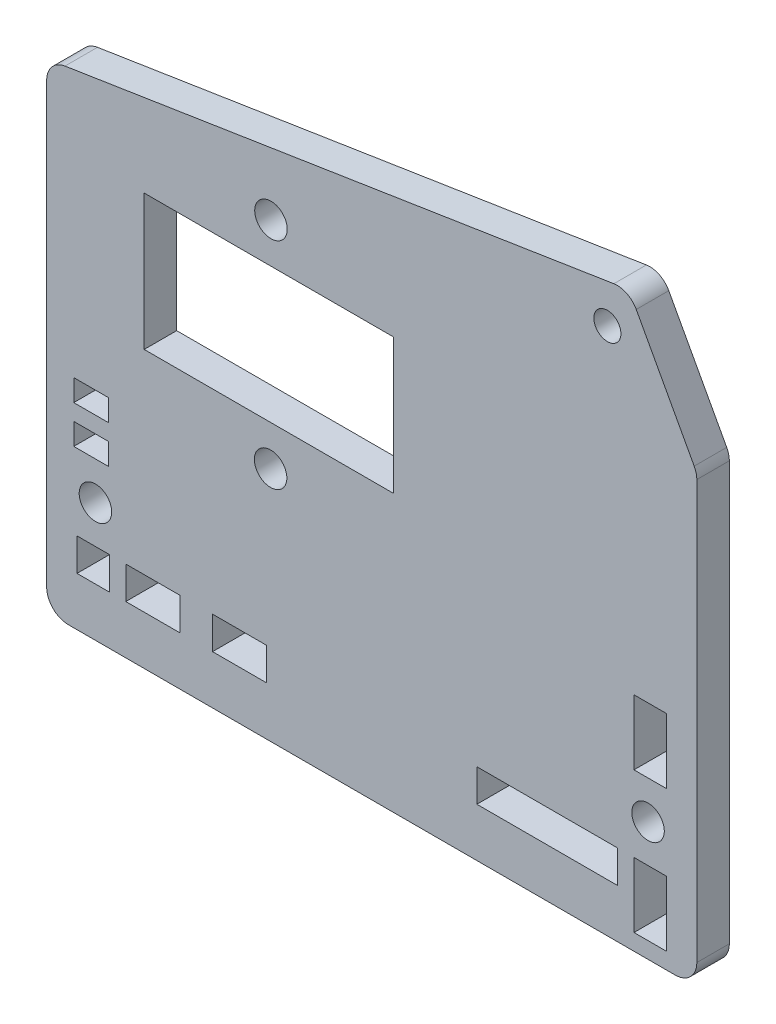
SolidWorks part; units mm, degrees
ref_plane "Plan de face" through (0, 0, 0) normal (0, 0, 1) x (1, 0, 0)
ref_plane "Plan de dessus" through (0, 0, 0) normal (0, 1, 0) x (1, 0, 0)
ref_plane "Plan de droite" through (0, 0, 0) normal (1, 0, 0) x (0, 0, -1)
sketch "Esquisse1" plane through (0, 0, 0) normal (0, 0, 1) x (1, 0, 0)
  line L0 (20.7, 21.5) -> (20.7, 41.7) construction
  line L1 (0, 0) -> (60, 0) construction
  line L2 (0, 0) -> (0, 44.2274) construction
  line L3 (0, 52.5) -> (60, 52.5) construction
  line L4 (60, 0) -> (60, 41.1061) construction
  line L5 (9, 38) -> (32, 38)
  line L6 (9, 38) -> (9, 25.5)
  line L7 (9, 25.5) -> (32, 25.5)
  line L8 (32, 38) -> (32, 25.5)
  line L9 (39.7, 7.5) -> (52.7, 7.5)
  line L10 (39.7, 7.5) -> (39.7, 4.5)
  line L11 (39.7, 4.5) -> (52.7, 4.5)
  line L12 (52.7, 7.5) -> (52.7, 4.5)
  line L13 (54.2, 7.5) -> (57.2, 7.5)
  line L14 (54.2, 7.5) -> (54.2, 1.5)
  line L15 (54.2, 1.5) -> (57.2, 1.5)
  line L16 (57.2, 7.5) -> (57.2, 1.5)
  line L17 (54.2, 20.5) -> (57.2, 20.5)
  line L18 (54.2, 20.5) -> (54.2, 14.5)
  line L19 (54.2, 14.5) -> (57.2, 14.5)
  line L20 (57.2, 20.5) -> (57.2, 14.5)
  line L21 (15.3085, 7.5) -> (20.3085, 7.5)
  line L22 (15.3085, 7.5) -> (15.3085, 4.5)
  line L23 (15.3085, 4.5) -> (20.3085, 4.5)
  line L24 (20.3085, 7.5) -> (20.3085, 4.5)
  line L25 (7.3, 7.5) -> (12.3085, 7.5)
  line L26 (7.3, 7.5) -> (7.3, 4.5)
  line L27 (7.3, 4.5) -> (12.3085, 4.5)
  line L28 (12.3085, 7.5) -> (12.3085, 4.5)
  line L29 (2.8, 7.5) -> (5.8, 7.5)
  line L30 (2.8, 7.5) -> (2.8, 4.5)
  line L31 (2.8, 4.5) -> (5.8, 4.5)
  line L32 (5.8, 7.5) -> (5.8, 4.5)
  line L33 (2.5, 16.5) -> (5.7, 16.5)
  line L34 (2.5, 16.5) -> (2.5, 14.5)
  line L35 (2.5, 14.5) -> (5.7, 14.5)
  line L36 (5.7, 16.5) -> (5.7, 14.5)
  line L37 (2.5, 20) -> (5.7, 20)
  line L38 (2.5, 20) -> (2.5, 18)
  line L39 (2.5, 18) -> (5.7, 18)
  line L40 (5.7, 20) -> (5.7, 18)
  line L41 (0, 42.5162) -> (0, 2)
  line L42 (2, 0) -> (58, 0)
  line L43 (60, 40.5982) -> (60, 2)
  line L44 (49.6105, 7.5) -> (66.4647, 7.5) construction
  line L45 (54.41, 51.4016) -> (59.7576, 41.5525)
  line L46 (1.6906, 44.4921) -> (52.3429, 52.4233)
  line L47 (60, 44.9776) -> (60, 52.5) construction
  circle A0 centre (51.7453, 48.75) radius 1.25
  circle A1 centre (20.7, 41.7) radius 1.5
  circle A2 centre (20.7, 21.5) radius 1.5 construction
  circle A3 centre (4.5, 11) radius 1.5
  circle A4 centre (55.5, 11) radius 1.5
  arc A5 (2, 0) -> (0, 2) centre (2, 2) cw
  arc A6 (60, 2) -> (58, 0) centre (58, 2) cw
  arc A7 (59.7576, 41.5525) -> (60, 40.5982) centre (58, 40.5982) cw
  arc A8 (52.3429, 52.4233) -> (54.41, 51.4016) centre (52.6523, 50.4473) cw
  arc A9 (0, 42.5162) -> (1.6906, 44.4921) centre (2, 42.5162) cw
  dimension "D7" = 2.5
  dimension "D8" = 3
  dimension "D9" = 3
  dimension "D11" = 19.2
  dimension "D12" = 2.5
  dimension "D39" = 3
  dimension "D40" = 2
  dimension "D43" = 3
  dimension "D57" = 2
  dimension "D1" = 60
  dimension "D2" = 52.5
  dimension "D3" = 12.5
  dimension "D4" = 23
  dimension "D5" = 28
  dimension "D6" = 25.5
  dimension "D10" = 19.2
  dimension "D13" = 2.2
  dimension "D14" = 3
  dimension "D15" = 6
  dimension "D16" = 1.5
  dimension "D17" = 7
  dimension "D18" = 6
  dimension "D19" = 3
  dimension "D20" = 2.8
  dimension "D21" = 2.8
  dimension "D22" = 4.5
  dimension "D23" = 13
  dimension "D24" = 3
  dimension "D25" = 1.5
  dimension "D26" = 5
  dimension "D27" = 5.0085
  dimension "D28" = 3
  dimension "D29" = 3
  dimension "D30" = 4.5
  dimension "D31" = 4.5
  dimension "D32" = 3
  dimension "D33" = 7.3
  dimension "D34" = 3
  dimension "D35" = 3
  dimension "D36" = 4.5
  dimension "D37" = 1.5
  dimension "D38" = 2.8
  dimension "D41" = 2
  dimension "D42" = 3
  dimension "D44" = 2
  dimension "D45" = 3
  dimension "D46" = 3.2
  dimension "D47" = 3.2
  dimension "D48" = 2
  dimension "D49" = 2
  dimension "D50" = 7
  dimension "D51" = 1.5
  dimension "D52" = 2.5
  dimension "D53" = 2.5
  dimension "D54" = 47.5
  dimension "D55" = 7.0047
  dimension "D56" = 98.899
  dimension "D58" = 151.5
base flange "Tôle de base pliée1" sketch "Esquisse1" thickness 3 reverse thickness direction no parameters "D1"=1.5
sketch "Esquisse2" plane through (0, 0, -3) normal (0, 0, -1) x (-1, 0, 0)
  circle A0 centre (-20.6658, 21.7998) radius 1.5
extrude "Enlèv. mat.-Extru.1" cut sketch "Esquisse2" against normal blind 10
sketch "Lignes de pliage1" [suppressed] plane through (0, 0, 0) normal (0, 1, 0) x (1, 0, 0)
sketch "Cube de visualisation1" [suppressed] plane through (0, 0, 0) normal (0, 1, 0) x (1, 0, 0)
sheet metal parameters "Tôlerie1" thickness 3 parameters "D1"=1.5
flat pattern "Etat déplié1" [suppressed]
sketch "Lignes de pliage2" plane through (0, 0, 0) normal (0, 1, 0) x (1, 0, 0)
sketch3d "Cube de visualisation2" [suppressed]
  line L0 (-2, 50.4468, 0) -> (58, 50.4468, 0) construction
  line L1 (-2, -2, 0) -> (58, -2, 0) construction
  line L2 (-2, 50.4468, 0) -> (-2, -2, 0) construction
  line L3 (58, 50.4468, 0) -> (58, -2, 0) construction
sketch "Esquisse2-1" [suppressed] plane through (0, 0, -3) normal (0, 0, -1) x (-1, 0, 0)
  circle A0 centre (-20.6658, 21.7998) radius 1.5
sheet metal parameters "Tôlerie2" thickness 3 parameters "D1"=1.5
flat pattern "Etat déplié1" [suppressed]
sketch "Lignes de pliage2" plane through (0, 0, 0) normal (0, 1, 0) x (1, 0, 0)
sketch3d "Cube de visualisation2" [suppressed]
  line L0 (-2, 50.4468, 0) -> (58, 50.4468, 0) construction
  line L1 (-2, -2, 0) -> (58, -2, 0) construction
  line L2 (-2, 50.4468, 0) -> (-2, -2, 0) construction
  line L3 (58, 50.4468, 0) -> (58, -2, 0) construction
sketch "Esquisse2-1" plane through (0, 0, -3) normal (0, 0, -1) x (-1, 0, 0)
  circle A0 centre (-20.6658, 21.7998) radius 1.5
sketch "Esquisse2-2" [suppressed] plane through (0, 0, -3) normal (0, 0, -1) x (-1, 0, 0)
  circle A0 centre (-20.6658, 21.7998) radius 1.5
sketch "Esquisse2-3" [suppressed] plane through (0, 0, -3) normal (0, 0, -1) x (-1, 0, 0)
  circle A0 centre (-20.6658, 21.7998) radius 1.5
